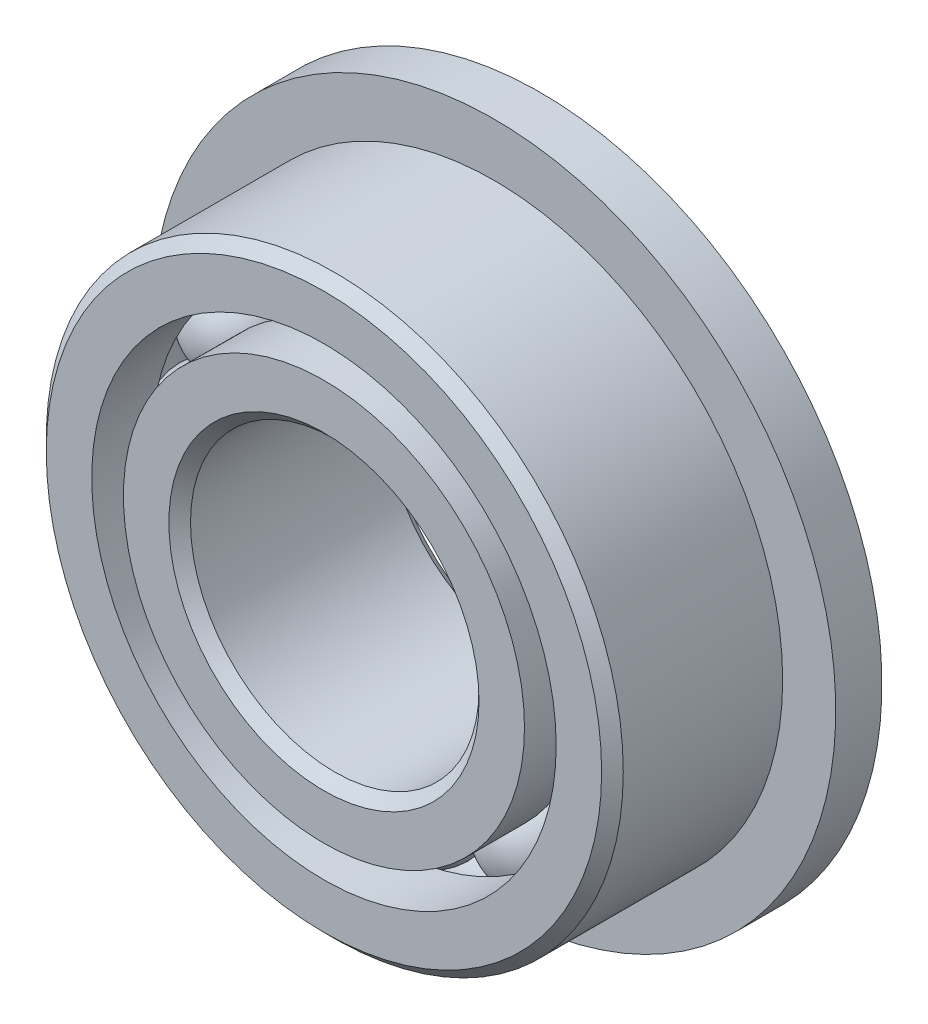
SolidWorks part; units mm, degrees
ref_plane "Front Plane" through (0, 0, 0) normal (0, 0, 1) x (1, 0, 0)
ref_plane "Top Plane" through (0, 0, 0) normal (0, 1, 0) x (1, 0, 0)
ref_plane "Right Plane" through (0, 0, 0) normal (1, 0, 0) x (0, 0, -1)
sketch "Sketch1" plane through (0, 0, 0) normal (1, 0, 0) x (0, 0, -1)
  line L0 (-1.1906, 0) -> (1.1906, 0) construction
  line L1 (0, 3.175) -> (0, -3.175) construction
  line L2 (1.0716, 3.175) -> (-1.0716, 3.175)
  line L3 (-1.0716, 3.175) -> (-1.1906, 3.0559)
  line L4 (-1.1906, 3.0559) -> (-1.1906, 2.5557)
  line L5 (-1.1906, 2.5557) -> (-0.5292, 2.5557)
  line L6 (1.1906, 2.5557) -> (0.5292, 2.5557)
  line L7 (1.1906, 3.0559) -> (1.1906, 2.5557)
  line L8 (1.0716, 3.175) -> (1.1906, 3.0559)
  line L9 (0, 3.175) -> (0, 2.3813) construction
  line L10 (0, 2.3813) -> (0, 1.5875) construction
  arc A0 (-0.5292, 2.5557) -> (0.5292, 2.5557) centre (0, 2.3813) cw
  point P14 (0, 1.5875)
  dimension "D3" = 1.0583
  dimension "D1" = 45
  dimension "Width" = 2.3813
  dimension "OD" = 6.35
  dimension "D2" = 0.1191
  dimension "Shaft Dia" = 3.175
  dimension "D4" = 0.1745
revolve "Revolve1" add sketch "Sketch1" angle 360 about L0
sketch "Sketch3" plane through (0, 0, 0) normal (1, 0, 0) x (0, 0, -1)
  line L0 (-1.0716, 3.175) -> (-1.1906, 3.0559) construction
  line L1 (-0.5292, 2.2068) -> (-1.1906, 2.2068)
  line L2 (-1.1906, 3.0559) -> (-1.1906, 2.5557) construction
  line L3 (-1.1906, 2.2068) -> (-1.1906, 1.7066)
  line L5 (-1.1906, 1.7066) -> (-1.0716, 1.5875)
  line L6 (-1.0716, 1.5875) -> (1.0716, 1.5875)
  line L7 (1.1906, 3.0559) -> (1.1906, 2.5557) construction
  line L8 (1.0716, 1.5875) -> (1.1906, 1.7066)
  line L10 (1.1906, 1.7066) -> (1.1906, 2.2068)
  line L11 (1.1906, 2.2068) -> (0.5292, 2.2068)
  line L13 (1.0716, 3.175) -> (1.1906, 3.0559) construction
  arc A1 (0.5292, 2.2068) -> (-0.5292, 2.2068) centre (0, 2.3812) cw
  arc A2 (0.5292, 2.5557) -> (-0.5292, 2.5557) centre (0, 2.3813) ccw construction
revolve "Revolve3" add sketch "Sketch3" angle 360 about L0
sketch "Sketch5" plane through (0, 0, 0) normal (1, 0, 0) x (0, 0, -1)
  line L0 (1.1906, 3.0559) -> (1.1906, 2.5557) construction
  line L1 (1.1906, 2.8058) -> (0.6826, 2.8058)
  line L2 (1.1906, 2.8058) -> (1.1906, 3.7592)
  line L3 (1.1906, 3.7592) -> (0.6826, 3.7592)
  line L4 (0.6826, 2.8058) -> (0.6826, 3.7592)
  line L5 (1.1906, 0) -> (-1.1906, 0) construction
  dimension "Th" = 0.508
  dimension "Flange OD" = 7.5184
revolve "Revolve5" add sketch "Sketch5" angle 360 about L5
sketch "Sketch4" plane through (0, 0, 0) normal (1, 0, 0) x (0, 0, -1)
  line L0 (-0.5572, 2.3812) -> (0.5572, 2.3812)
  arc A2 (-0.5572, 2.3812) -> (0.5572, 2.3812) centre (0, 2.3813) cw
  arc A3 (0.5292, 2.5557) -> (-0.5292, 2.5557) centre (0, 2.3813) ccw construction
revolve "Revolve4" add sketch "Sketch4" angle 360 about L0
ref_axis "Axis1" through (0, 0, -1.1906) along (0, 0, 1)
pattern_circular "CirPattern1" count 12 every 30 about axis through (0, 0, -1.1906) along (0, 0, 1) of bodies 104
equation "\"D2@Sketch1\" = \"Width@Sketch1\"*.05"
equation "\"D3@Sketch1\" = \"Width@Sketch1\"/2.25"
equation "\"D4@Sketch1\" = (((\"OD@Sketch1\"-\"Width@Sketch1\")/2)/3.25)/3.5"
equation "\"D2@CirPattern1\" = 360/\"Balls@CirPattern1\""
